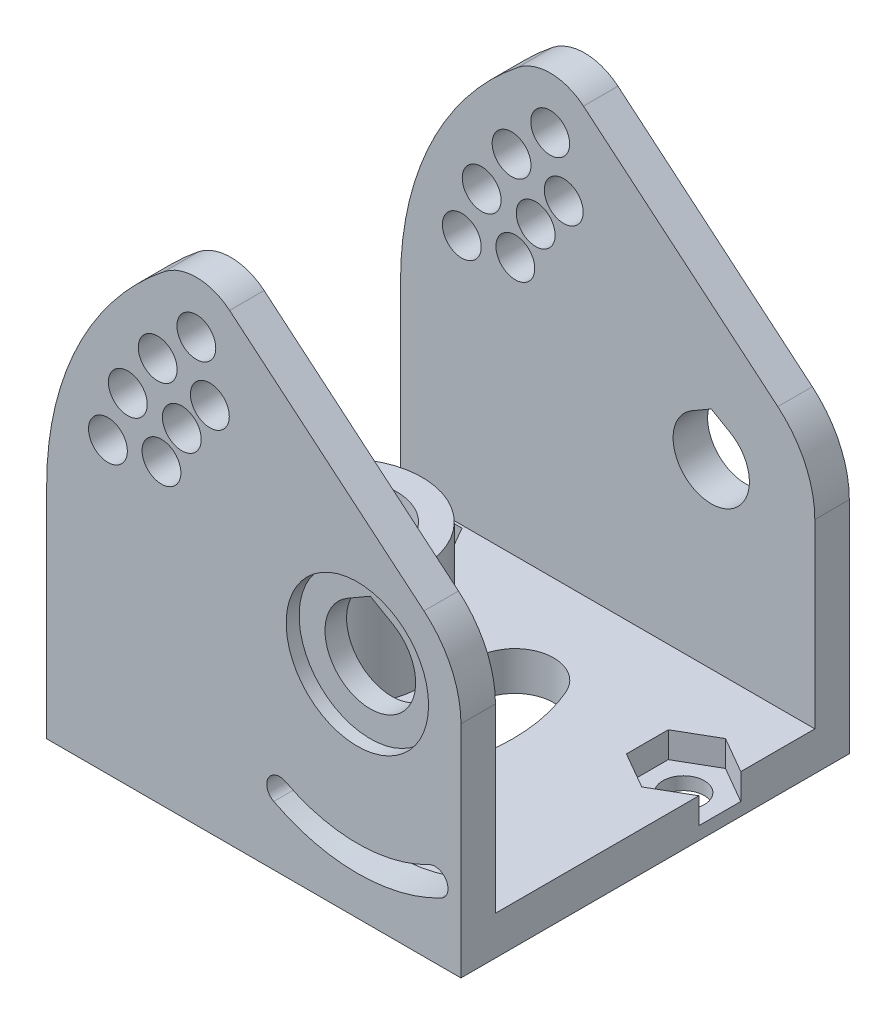
SolidWorks part; units mm, degrees
ref_plane "Front Plane" through (0, 0, 0) normal (0, 0, 1) x (1, 0, 0)
ref_plane "Top Plane" through (0, 0, 0) normal (0, 1, 0) x (1, 0, 0)
ref_plane "Right Plane" through (0, 0, 0) normal (1, 0, 0) x (0, 0, -1)
sketch "Sketch1" plane through (0, 0, 0) normal (0, 1, 0) x (1, 0, 0)
  line L1 (0, -15) -> (32, -15)
  line L2 (0, -15) -> (0, 15)
  line L3 (0, 15) -> (32, 15)
  line L4 (32, -15) -> (32, 15)
  line L5 (4.9497, 6.5334) -> (6.5663, 9.3334)
  line L6 (6.5663, 9.3334) -> (4.9497, 12.1334)
  line L7 (4.9497, 12.1334) -> (1.7166, 12.1334)
  line L8 (1.7166, 12.1334) -> (0.1, 9.3334)
  line L9 (0.1, 9.3334) -> (1.7166, 6.5334)
  line L10 (1.7166, 6.5334) -> (4.9497, 6.5334)
  line L16 (8, 0) -> (18, 0) construction
  line L17 (29.2, 8.2332) -> (26.4, 6.6166)
  line L18 (26.4, 6.6166) -> (26.4, 3.3834)
  line L19 (26.4, 3.3834) -> (29.2, 1.7668)
  line L20 (29.2, 1.7668) -> (32, 3.3834)
  line L21 (32, 3.3834) -> (32, 6.6166)
  line L22 (32, 6.6166) -> (29.2, 8.2332)
  circle A0 centre (3.3332, 9.3334) radius 1.6
  circle A1 centre (3.3332, 9.3334) radius 2.8 construction
  circle A2 centre (8, 0) radius 6
  circle A3 centre (8, 0) radius 4.05
  circle A4 centre (8, 0) radius 1.5
  circle A6 centre (29.2, 5) radius 1.6
  circle A7 centre (29.2, 5) radius 2.8 construction
  arc A8 (17.1652, 4) -> (17.1652, -4) centre (8, 0) cw construction
  arc A9 (19.9147, -5.2) -> (19.9147, 5.2) centre (8, 0) ccw
  arc A10 (14.4156, -2.8) -> (14.4156, 2.8) centre (8, 0) ccw
  arc A11 (14.4156, -2.8) -> (19.9147, -5.2) centre (17.1652, -4) ccw
  arc A12 (19.9147, 5.2) -> (14.4156, 2.8) centre (17.1652, 4) ccw
  point P4 (0, 0)
  point P21 (18, 0)
  dimension "D3" = 3.2
  dimension "D7" = 3
  dimension "D8" = 8.1
  dimension "D9" = 12
  dimension "D11" = 3.2
  dimension "D14" = 8
  dimension "D16" = 6
  dimension "D1" = 30
  dimension "D2" = 32
  dimension "D4" = 5.6
  dimension "D5" = 5.6666
  dimension "D6" = 0.1
  dimension "D10" = 8
  dimension "D12" = 5.6
  dimension "D13" = 10
  dimension "D15" = 10
extrude "Boss-Extrude1" add sketch "Sketch1" along normal blind 3 contours L1 L4 L3 L2 L10 L9 L8 L7 L6 L5 region at (0.4386, 0, 0)
extrude "Boss-Extrude5" add sketch "Sketch1<3>" along normal blind 1 contours L9 L10 L5 L6 L7 L8 A0 | L17 L18 L19 L20 L21 L22 | A6 region at (3.3332, 0, -6.6189)
sketch "Sketch1<3>" plane through (0, 0, 0) normal (0, 1, 0) x (1, 0, 0) same geometry as "Sketch1"
extrude "Boss-Extrude6" add sketch "Sketch1<6>" along normal blind 11 contours A2 A3 region at (2.1697, 0, 0)
sketch "Sketch1<6>" plane through (0, 0, 0) normal (0, 1, 0) x (1, 0, 0) same geometry as "Sketch1"
extrude "Boss-Extrude7" add sketch "Sketch1<7>" along normal blind 7 contours A3 A4 region at (4.0646, 0, 0)
sketch "Sketch1<7>" plane through (0, 0, 0) normal (0, 1, 0) x (1, 0, 0) same geometry as "Sketch1"
sketch "Sketch2" plane through (0, 0, 15) normal (0, 0, 1) x (1, 0, 0)
  line L0 (29.1423, 23.1284) -> (14.131, 35.7244)
  line L1 (32, 3) -> (32, 17)
  line L12 (0, 3) -> (32, 3)
  line L14 (0, 3) -> (0, 17)
  line L15 (24, 17) -> (11.5598, 32.6602) construction
  line L16 (24, 17) -> (8.5757, 29.7315) construction
  line L17 (8.5757, 29.7315) -> (11.5598, 32.6602) construction
  line L18 (11.5598, 32.6602) -> (12.6041, 28.6116) construction
  line L19 (12.6041, 28.6116) -> (8.5757, 29.7315) construction
  line L20 (8.5757, 29.7315) -> (10.4389, 25.9885) construction
  line L21 (10.4389, 25.9885) -> (6.2657, 26.2464) construction
  line L22 (6.2657, 26.2464) -> (8.8665, 22.9725) construction
  line L23 (8.8665, 22.9725) -> (4.7308, 22.3572) construction
  line L24 (32, 3) -> (32, 0) construction
  arc A0 (32, 17) -> (29.1423, 23.1284) centre (24, 17) ccw
  arc A17 (9.0718, 35.7922) -> (0, 17) centre (24, 17) ccw
  arc A18 (14.131, 35.7244) -> (9.0718, 35.7922) centre (11.5598, 32.6602) ccw
  circle A19 centre (11.5598, 32.6602) radius 1.5
  circle A20 centre (8.5757, 29.7315) radius 1.5
  circle A21 centre (6.2657, 26.2464) radius 1.5
  circle A22 centre (4.7308, 22.3572) radius 1.5
  circle A23 centre (12.6041, 28.6116) radius 1.5
  circle A24 centre (10.4389, 25.9885) radius 1.5
  circle A25 centre (8.8665, 22.9725) radius 1.5
  dimension "D1" = 4
  dimension "D2" = 40
  dimension "D3" = 4
  dimension "D5" = 3
  dimension "D6" = 8
  dimension "D4" = 12
  dimension "D7" = 14
extrude "Boss-Extrude2" add sketch "Sketch2" against normal blind 2.666
mirror "Mirror1" about plane through (0, 0, 0) normal (0, 0, 1) of "Boss-Extrude2"
sketch "Sketch3" plane through (0, 0, 15) normal (0, 0, 1) x (1, 0, 0)
  line L1 (22.25, 20.0311) -> (24, 21.0415)
  line L2 (24, 21.0415) -> (25.75, 20.0311)
  line L3 (24, 17) -> (24, 4) construction
  arc A0 (22.25, 20.0311) -> (25.75, 20.0311) centre (24, 17) ccw
  circle A1 centre (24, 17) radius 5.5
  arc A2 (18, 5.4674) -> (30, 5.4674) centre (24, 17) ccw construction
  arc A3 (17.5385, 4.5803) -> (30.4615, 4.5803) centre (24, 17) ccw
  arc A4 (18.4615, 6.3546) -> (29.5385, 6.3546) centre (24, 17) ccw
  arc A5 (18.4615, 6.3546) -> (17.5385, 4.5803) centre (18, 5.4674) ccw
  arc A6 (30.4615, 4.5803) -> (29.5385, 6.3546) centre (30, 5.4674) ccw
  point P2 (24, 4)
  dimension "D1" = 7
  dimension "D5" = 11
  dimension "D2" = 2
  dimension "D3" = 13
  dimension "D4" = 30
  dimension "D6" = 12
extrude "Cut-Extrude1" cut sketch "Sketch3" against normal up to surface (2.666 mm away) contours L1 A0 L2 | A4 A6 A3 A5 region at (24, 17.0609, 15) up to face at (10.3665, 22.9725, 12.334)
sketch "Sketch4" plane through (0, 0, -12.334) normal (0, 0, 1) x (1, 0, 0)
  line L1 (22.5275, 19.5504) -> (24, 20.4006)
  line L2 (24, 20.4006) -> (25.4725, 19.5504)
  arc A0 (22.5275, 19.5504) -> (25.4725, 19.5504) centre (24, 17) ccw
  dimension "D1" = 5.89
  dimension "D4" = 30
extrude "Cut-Extrude2" cut sketch "Sketch4" against normal up to surface (2.666 mm away) up to face at (16.4125, 18.7001, -15)
extrude "Cut-Extrude4" cut sketch "Sketch3<3>" against normal blind 1
sketch "Sketch3<3>" plane through (0, 0, 15) normal (0, 0, 1) x (1, 0, 0) same geometry as "Sketch3"
equation "\"margin_around_hole\"= 4mm"
equation "\"panel_mount_diam\"= 7mm"
equation "\"shaft_diam\"= 5.5mm"
equation "\"magnet_separation\"=16.5"
equation "\"magnet_diam\"= 8mm"
equation "\"magnet_height\"= 4mm"
equation "\"side_thickness\"= 2.6666mm"
equation "\"base_thickness\"= 3mm"
equation "\"D1@Boss-Extrude1\"=\"base_thickness\""
equation "\"D1@Boss-Extrude6\"=\"base_thickness\"+\"magnet_height\"+4"
equation "\"D1@Boss-Extrude7\"=\"base_thickness\"+4"
